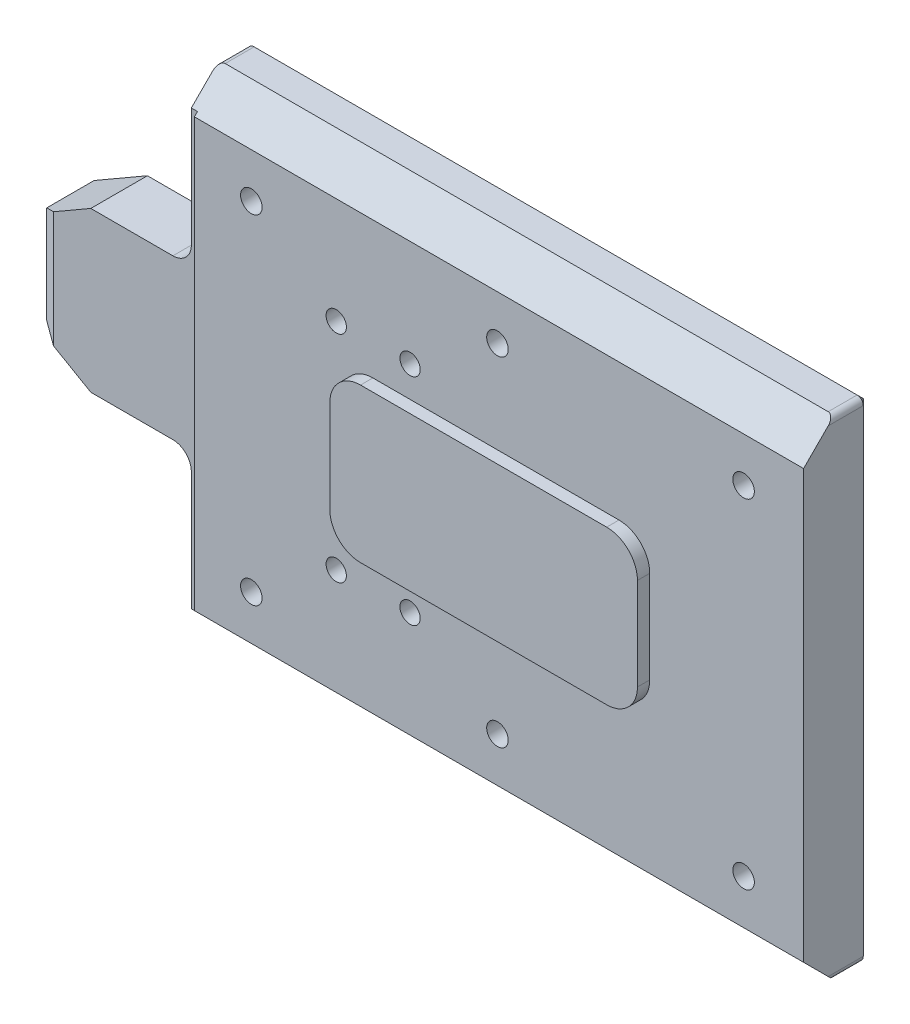
SolidWorks part; units mm, degrees
note: '?' marks a value the reader was unsure of.
material "UHMW PE"
ref_plane "Front Plane" through (0, 0, 0) normal (0, 0, 1) x (1, 0, 0)
ref_plane "Top Plane" through (0, 0, 0) normal (0, 1, 0) x (1, 0, 0)
ref_plane "Right Plane" through (0, 0, 0) normal (1, 0, 0) x (0, 0, -1)
ref_axis "Axis1" through (0, 0, -88.99) along (0, 0, 1)?
ref_axis "Axis2" through (0, -55, 0) along (0, 1, 0)?
ref_axis "Axis3" through (-88.99, 0, 0) along (1, 0, 0)?
sketch "Sketch1" plane through (0, 0, 0) normal (0, 0, 1) x (1, 0, 0)
  line L0 (0, 38.75) -> (0, 12.9375)
  line L1 (0, 12.9375) -> (-25, 12.9375)
  line L2 (-25, 12.9375) -> (-25, -12.9375)
  line L3 (1, 39.75) -> (99, 39.75)
  line L4 (100, 38.75) -> (100, -38.75)
  line L5 (-25, 0) -> (100, 0) construction
  line L6 (1, -39.75) -> (99, -39.75)
  line L7 (0, -38.75) -> (0, -12.9375)
  line L8 (0, -12.9375) -> (-25, -12.9375)
  arc A0 (1, -39.75) -> (0, -38.75) centre (1, -38.75) cw
  arc A1 (99, -39.75) -> (100, -38.75) centre (99, -38.75) ccw
  arc A2 (99, 39.75) -> (100, 38.75) centre (99, 38.75) cw
  arc A3 (0, 38.75) -> (1, 39.75) centre (1, 38.75) cw
  point P13 (0, -39.75)
  point P16 (100, -39.75)
  point P19 (100, 39.75)
  point P22 (0, 39.75)
  dimension "D4" = 1
  dimension "D1" = 79.5
  dimension "D2" = 25
  dimension "D3" = 100
  dimension "D5" = 25.875
extrude "Boss-Extrude1" add sketch "Sketch1" along normal blind 12.7
chamfer "Chamfer1" distance 5 angle 60 2 edges at (-25, -12.9375, 6.35) (-25, 12.9375, 6.35) first distance on face at (-25, 0, 6.35)
hole_wizard "CBORE for M6 Pan Head Machine Screw1" [suppressed] positions "Sketch3" profile "Sketch2" counterbore size "M6" standard "ANSI Metric"
sketch "Sketch3" plane through (0, 0, 0) normal (0, 0, -1) x (-1, 0, 0)
  line L0 (-90.25, 27.5) -> (-10.25, 27.5) construction
  line L3 (0, 0) -> (-100, 0) construction
  line L4 (-100, -27.75) -> (-100, 27.75) construction
  line L6 (0, 27.75) -> (0, 14.625) construction
  point P0 (-90.25, 27.5)
  point P3 (-90.25, -27.5)
  point P6 (-10.25, -27.5)
  point P9 (-10.25, 27.5)
  point P13 (-50.25, 27.5)
  point P15 (-50.25, -27.5)
  dimension "D1" = 40
  dimension "D2" = 55
  dimension "D3" = 10.25
sketch "Sketch2" plane through (90, 25, 0) normal (1, 0, 0) x (0, 1, 0)
  line L0 (0, 0) -> (0, 12.7)
  line L1 (0, 12.7) -> (3.3, 12.7)
  line L3 (3.3, 12.7) -> (3.3, 7.1)
  line L4 (3.3, 7.1) -> (6.5, 7.1)
  line L5 (6.5, 7.1) -> (6.5, 0)
  line L7 (6.5, 0) -> (0, 0)
  line L11 (0, -6.35) -> (0, 107.95) construction
  dimension "Thru Hole Dia." = 6.6
  dimension "Thru Hole Depth" = 12.7
  dimension "C'Bore Dia." = 13
  dimension "C'Bore Depth" = 7.1
hole_wizard "Tap Drill for M4x0.7 Tap1" positions "Sketch5" profile "Sketch4" hole size "M4x0.7" standard "ANSI Metric" end condition through all
sketch "Sketch5" plane through (0, 0, 0) normal (0, 0, -1) x (-1, 0, 0)
  line L3 (0, 0) -> (-24.05, 0) construction
  line L4 (-30.05, -17.5) -> (-30.05, 0) construction
  point P17 (-24.05, 17.5)
  point P21 (-24.05, -17.5)
  point P29 (-36.05, 17.5)
  point P30 (-36.05, -17.5)
  dimension "D1" = 24.05
  dimension "D2" = 35
  dimension "D3" = 12
sketch "Sketch4" plane through (24.05, 17.5, 0) normal (1, 0, 0) x (0, 1, 0)
  line L0 (0, 0) -> (0, 12.7)
  line L1 (0, 12.7) -> (1.65, 12.7)
  line L2 (1.65, 12.7) -> (1.65, 0)
  line L5 (1.65, 0) -> (0, 0)
  line L11 (0, -6.35) -> (0, 107.95) construction
  dimension "Thru Hole Dia." = 3.3
  dimension "Thru Hole Depth" = 12.7
sketch "Sketch9" plane through (0, 0, 12.7) normal (0, 0, 1) x (1, 0, 0)
  line L0 (0, 0) -> (50, 0) construction
  line L2 (70, -12.5) -> (30, -12.5)
  line L3 (75, -7.5) -> (75, 7.5)
  line L4 (70, 12.5) -> (30, 12.5)
  line L5 (25, -7.5) -> (25, 7.5)
  line L6 (75, -12.5) -> (25, 12.5) construction
  line L7 (75, 12.5) -> (25, -12.5) construction
  line L10 (0, 12.9375) -> (-16.3397, 12.9375)
  line L11 (-16.3397, 12.9375) -> (-25, 7.9375)
  line L12 (-25, 7.9375) -> (-25, -7.9375)
  line L13 (-25, -7.9375) -> (-16.3397, -12.9375)
  line L14 (-16.3397, -12.9375) -> (0, -12.9375)
  line L15 (0, -12.9375) -> (0, -38.75)
  line L16 (1, -39.75) -> (99, -39.75)
  line L17 (100, -38.75) -> (100, 38.75)
  line L18 (99, 39.75) -> (1, 39.75)
  line L19 (0, 38.75) -> (0, 12.9375)
  line L20 (0, 12.9375) -> (-16.3397, 12.9375)
  line L21 (-16.3397, 12.9375) -> (-25, 7.9375)
  line L22 (-25, 7.9375) -> (-25, -7.9375)
  line L23 (-25, -7.9375) -> (-16.3397, -12.9375)
  line L24 (-16.3397, -12.9375) -> (0, -12.9375)
  line L25 (0, -12.9375) -> (0, -38.75)
  line L26 (1, -39.75) -> (99, -39.75)
  line L27 (100, -38.75) -> (100, 38.75)
  line L28 (99, 39.75) -> (1, 39.75)
  line L29 (0, 38.75) -> (0, 12.9375)
  arc A0 (75, 7.5) -> (70, 12.5) centre (70, 7.5) ccw
  arc A1 (70, -12.5) -> (75, -7.5) centre (70, -7.5) ccw
  arc A2 (30, -12.5) -> (25, -7.5) centre (30, -7.5) cw
  arc A3 (30, 12.5) -> (25, 7.5) centre (30, 7.5) ccw
  arc A4 (0, -38.75) -> (1, -39.75) centre (1, -38.75) ccw
  arc A5 (99, -39.75) -> (100, -38.75) centre (99, -38.75) ccw
  arc A6 (100, 38.75) -> (99, 39.75) centre (99, 38.75) ccw
  arc A7 (1, 39.75) -> (0, 38.75) centre (1, 38.75) ccw
  arc A8 (0, -38.75) -> (1, -39.75) centre (1, -38.75) ccw
  arc A9 (99, -39.75) -> (100, -38.75) centre (99, -38.75) ccw
  arc A10 (100, 38.75) -> (99, 39.75) centre (99, 38.75) ccw
  arc A11 (1, 39.75) -> (0, 38.75) centre (1, 38.75) ccw
  dimension "D4" = 5
  dimension "D2" = 25
  dimension "D3" = 50
  dimension "D5" = 50
  dimension "D1" = 0
extrude "Cut-Extrude2" cut sketch "Sketch9" against normal blind 2
sketch "Sketch6" plane through (0, 0, 10.7) normal (0, 0, 1) x (1, 0, 0)
  line L0 (-25, 7.9375) -> (-25, -7.9375) construction
  line L1 (1, 39.75) -> (-25, 39.75)
  line L2 (1, 39.75) -> (1, -39.75)
  line L3 (1, -39.75) -> (-25, -39.75)
  line L4 (-25, 39.75) -> (-25, -39.75)
  line L5 (0, 0) -> (1, 0) construction
  line L6 (0, 38.75) -> (0, 12.9375) construction
  line L7 (99, 39.75) -> (1, 39.75) construction
  dimension "D1" = 1
extrude "Cut-Extrude1" cut sketch "Sketch6" against normal blind 0.5
fillet "Fillet1" radius 3 2 edges at (0, -12.9375, 5.1) (0, 12.9375, 5.1)
chamfer "Chamfer2" distance 1 angle 45 16 edges at (-0.8787, -13.8162, 0) (0, -27.3437, 0) (0.2929, -39.4571, 0) (50, -39.75, 0) (99.7071, -39.4571, 0) (100, 0, 0) (99.7071, 39.4571, 0) (50, 39.75, 0) (0.2929, 39.4571, 0) (0, 27.3437, 0) (-0.8787, 13.8162, 0) (-9.6699, 12.9375, 0) (-20.6699, 10.4375, 0) (-25, 0, 0) (-20.6699, -10.4375, 0) (-9.6699, -12.9375, 0)
chamfer "Chamfer3" distance 1.5 angle 60 1 edges at (-25, 0, 10.2) first distance on face at (-25, 0, 5.6)
hole_wizard "Tap Drill for M5x0.8 Tap1" positions "Sketch8" profile "Sketch7" hole size "M5x0.8" standard "ANSI Metric" end condition through all
sketch "Sketch8" plane through (0, 0, 0) normal (0, 0, -1) x (-1, 0, 0)
  point P0 (-90.25, 27.5)
  point P3 (-50.25, 27.5)
  point P6 (-10.25, 27.5)
  point P9 (-10.25, -27.5)
  point P12 (-50.25, -27.5)
  point P15 (-90.25, -27.5)
sketch "Sketch7" plane through (90.25, 27.5, 0) normal (1, 0, 0) x (0, 1, 0)
  line L0 (0, 0) -> (0, 12.7)
  line L1 (0, 12.7) -> (1.75, 12.7)
  line L2 (1.75, 12.7) -> (1.75, 0)
  line L5 (1.75, 0) -> (0, 0)
  line L11 (0, -6.35) -> (0, 107.95) construction
  dimension "Thru Hole Dia." = 3.5
  dimension "Thru Hole Depth" = 12.7
chamfer "Chamfer4" distance 5 angle 45 2 edges at (50, -39.75, 10.7) (50, 39.75, 10.7) tangent propagation no
fillet "Fillet2" [suppressed] radius 1.5
